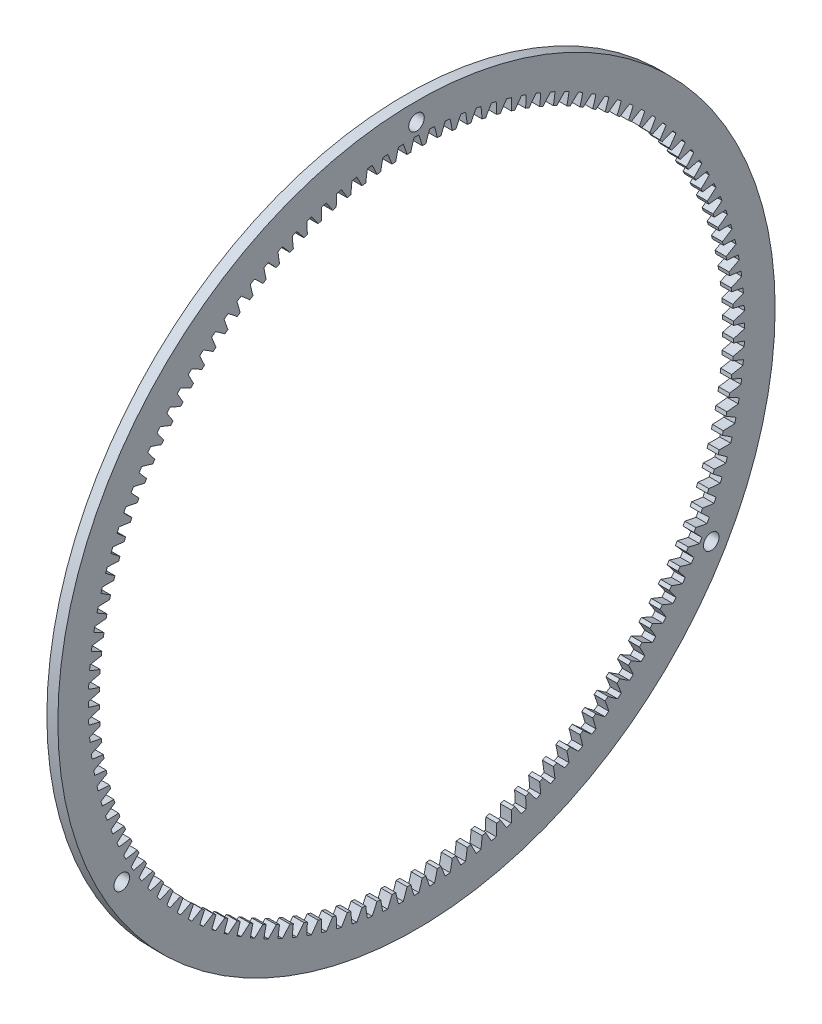
SolidWorks part; units mm, degrees
material "PVC 0.007 Plasticized"
ref_plane "Plane1" through (0, 0, 0) normal (0, 0, 1) x (1, 0, 0)
ref_plane "Plane2" through (0, 0, 0) normal (0, 1, 0) x (1, 0, 0)
ref_plane "Plane3" through (0, 0, 0) normal (1, 0, 0) x (0, 0, -1)
other "Configuration Table"
sketch "HoldingSke" plane through (0, 0, 0) normal (0, 1, 0) x (1, 0, 0)
  line L0 (0, 0) -> (-203.951, -226.5105)
  line L1 (-15, 0) -> (100, 0) construction
  line L2 (0, 0) -> (-2.1039, 2.3779)
  line L3 (0, 0) -> (-11.863, 4.5341)
  line L4 (0, 0) -> (-5.7786, 6.4178)
  line L5 (0, 0) -> (-23.7986, -8.8762)
  line L6 (0, 0) -> (-10.5278, -7.1032)
  line L7 (-2.1039, 2.3779) -> (3.3635, 27.1825)
  line L8 (-76.2, 54.61) -> (-54.61, 54.61)
  line L9 (-67.7845, 28.3722) -> (-49.3413, 33.142)
  line L10 (-76.2, 71.12) -> (104.1128, 71.12)
  line L11 (0, 0) -> (-4.7625, 0)
  line L12 (-76.2, 101.6) -> (-76.1147, 101.6)
  line L13 (24.9733, 27.94) -> (52.9518, 28.4284)
  line L14 (24.9733, 27.94) -> (24.9746, 27.94)
  line L15 (24.9733, 27.94) -> (100.4006, 29.5858)
  circle A0 centre (0, 0) radius 155.575
  circle A1 centre (0, 0) radius 12.7
  circle A2 centre (0, 0) radius 12.7
  dimension "Num_teeth" = 132
  dimension "Pitch_radius" = 180.3128
  dimension "Width" = 4.7625
  dimension "Diameter" = 311.15
sketch "BasProSke" plane through (0, 0, 0) normal (0, 1, 0) x (1, 0, 0)
  line L0 (-10, 0) -> (60, 0) construction
  line L1 (0, 137.5833) -> (0, 155.575)
  line L2 (0, 137.5833) -> (4.7625, 137.5833)
  line L3 (4.7625, 137.5833) -> (4.7625, 155.575)
  line L4 (4.7625, 155.575) -> (0, 155.575)
  dimension "Thickness" = 4.7625
  dimension "Diameter" = 311.15
revolve "Base-Revolve" add sketch "BasProSke" angle 360 about L0
sketch "TooCutSke" plane through (0, 0, 0) normal (1, 0, 0) x (0, 0, -1)
  line L3 (1.8757, 139.6874) -> (1.8757, 53.6633) construction
  line L4 (0, 0) -> (0, 59.563) construction
  line L5 (0, 0) -> (-1.626, 68.3081) construction
  line L6 (-65.203, 120.2076) -> (34.9353, 122.5913) construction
  circle A0 centre (0, 0) radius 139.7 construction
  circle A1 centre (0, 0) radius 142.3471 construction
  circle A2 centre (0, 0) radius 121.7252 construction
  circle A3 centre (0, 0) radius 137.5579 construction
  arc A4 (2.4635, 137.5359) -> (1.0468, 142.3433) centre (-65.203, 120.2076) ccw
  arc A5 (2.4635, 137.5359) -> (-2.4635, 137.5359) centre (0, 0) ccw
  arc A6 (1.0468, 142.3433) -> (-1.0468, 142.3433) centre (0, 0) ccw
  arc A7 (-1.0468, 142.3433) -> (-2.4635, 137.5359) centre (65.203, 120.2076) ccw
extrude "ToothCut" cut sketch "TooCutSke" along normal through all
fillet "Breaks" [suppressed] radius 0.2117
fillet "RootFillets" [suppressed] radius 0.5304
pattern_circular "TeethCuts" count 132 every 2.727 about axis through (-10, 0, 0) along (1, 0, 0) of "RootFillets", "Breaks", "ToothCut"
sketch "Sketch1" plane through (4.7625, 0, 0) normal (1, 0, 0) x (0, 0, -1)
  line L0 (0, 0) -> (0, 147.6375) construction
  line L1 (0, 0) -> (127.8578, -73.8188) construction
  line L2 (0, 0) -> (-127.8578, -73.8187) construction
  circle A0 centre (0, 0) radius 147.6375 construction
  point P8 (0, 0)
  dimension "D1" = 295.275
  dimension "D2" = 3
hole_wizard "H (0.266) Diameter Hole1" positions "Sketch2" profile "Sketch3" hole size "H" standard "ANSI Inch" end condition through all
sketch "Sketch2" plane through (4.7625, 0, 0) normal (1, 0, 0) x (0, 0, -1)
  circle A0 centre (0, 0) radius 147.6375 construction
  point P0 (0, 147.6375)
  point P5 (-127.8578, -73.8187)
  point P8 (127.8578, -73.8188)
sketch "Sketch3" plane through (4.7625, 147.6375, 0) normal (0, 1, 0) x (0, 0, -1)
  line L0 (0, 0) -> (0, 4.7625)
  line L1 (0, 4.7625) -> (3.3782, 4.7625)
  line L2 (3.3782, 4.7625) -> (3.3782, 0)
  line L5 (3.3782, 0) -> (0, 0)
  line L11 (0, -6.35) -> (0, 107.95) construction
  dimension "Thru Hole Dia." = 6.7564
  dimension "Thru Hole Depth" = 4.7625
equation "' \"Pitch@HoldingSke\" = 4"
equation "' \"Num_teeth@HoldingSke\" = 24"
equation "' \"Ap@HoldingSke\" =  14.5"
equation "' \"Ap@HoldingSke\" = 14.5"
equation "' \"Width@HoldingSke\" = 0.5"
equation "' \"Diameter@HoldingSke\" = 8"
equation "' \"Show_teeth@HoldingSke\" = 100"
equation "' \"Backlash@HoldingSke\" = 0.009"
equation "' \"Addendum_fac@HoldingSke\" = 1.0"
equation "' \"Dedendum_fac@HoldingSke\" = 1.25"
equation "' \"Dedendum_add@HoldingSke\" = 0.00005"
equation "' \"Clearance_fac@HoldingSke\" = 0.25"
equation "\"Overcut_dia@TooCutSke\" = (\"Num_teeth@HoldingSke\" - 2 * \"Addendum_fac@HoldingSke\") / \"Pitch@HoldingSke\" - 0.002"
equation "\"Pitch_dia@TooCutSke\" = \"Num_teeth@HoldingSke\" / \"Pitch@HoldingSke\""
equation "\"Base_dia@TooCutSke\" = \"Num_teeth@HoldingSke\" / \"Pitch@HoldingSke\" * cos((\"Ap@HoldingSke\"  * 3.14159265 / 180)) * 0.90"
equation "\"Root_dia@TooCutSke\" = \"Num_teeth@HoldingSke\"  / \"Pitch@HoldingSke\" + 2 *  \"Dedendum_fac@HoldingSke\"/ \"Pitch@HoldingSke\" + \"Dedendum_add@HoldingSke\" * 2"
equation "\"Half_ang@TooCutSke\" = 180 / \"Num_teeth@HoldingSke\""
equation "\"Half_CT@TooCutSke\" = \"Num_teeth@HoldingSke\" / \"Pitch@HoldingSke\" * sin((3.14159265 / 2 / \"Num_teeth@HoldingSke\")) / 2 + 10 * \"Backlash@HoldingSke\" / 4"
equation "\"Flank_rad@TooCutSke\" = \"Num_teeth@HoldingSke\" / \"Pitch@HoldingSke\" / 4"
equation "\"Radius@RootFillets\"= \"Clearance_fac@HoldingSke\" / \"Pitch@HoldingSke\" + \"Dedendum_add@HoldingSke\""
equation "\"Break_rad@Breaks\" = 0.02 / \"Pitch@HoldingSke\" * 5"
equation "\"Num_teeth@TeethCuts\" = int( \"Show_teeth@HoldingSke\" ) + 1"
equation "\"Num_teeth@TeethCuts\" = ((sgn( \"Num_teeth@TeethCuts\" - \"Num_teeth@HoldingSke\" )-1)*( \"Num_teeth@TeethCuts\" - \"Num_teeth@HoldingSke\" ))/-2+ \"Num_teeth@HoldingSke\""
equation "\"Num_teeth@TeethCuts\" = ((sgn( \"Num_teeth@TeethCuts\" - 2.0)+1)*( \"Num_teeth@TeethCuts\" - 2.0))/2 +2.0"
equation "\"Angle@TeethCuts\" = 360.0 / \"Num_teeth@HoldingSke\""
equation "\"Diameter@BasProSke\" = \"Num_teeth@HoldingSke\"  / \"Pitch@HoldingSke\" + 2 *  \"Dedendum_fac@HoldingSke\"/ \"Pitch@HoldingSke\" + \"Dedendum_add@HoldingSke\" * 2 + 0.002"
equation "\"Diameter@BasProSke\" = ((sgn( \"Diameter@BasProSke\"  - \"Diameter@HoldingSke\" )+1)*( \"Diameter@BasProSke\"  - \"Diameter@HoldingSke\" ))/2 + \"Diameter@HoldingSke\""
equation "\"Inside_diameter@BasProSke\" =  (\"Num_teeth@HoldingSke\" - 2 * \"Addendum_fac@HoldingSke\") / \"Pitch@HoldingSke\" "
equation "\"Thickness@BasProSke\"  = \"Width@HoldingSke\""
